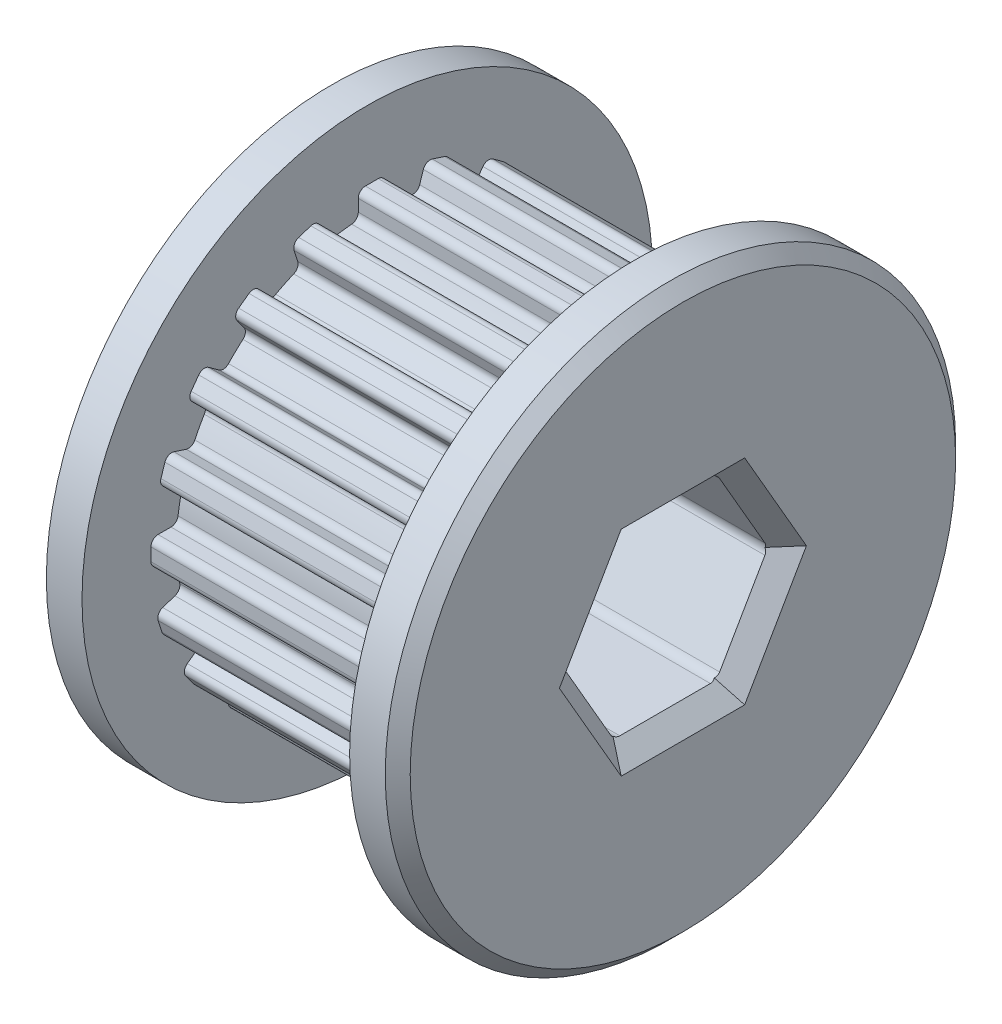
SolidWorks part; units mm, degrees
other "Markup1"
sketch "Sketch5" plane through (2.4288, -10.5, -8) normal (0.9999, -0.0054, -0.0108) x (-0.0109, -0.7875, -0.6163)
material "2024-T4"
ref_plane "Front Plane" through (0, 0, 0) normal (0, 0, 1) x (1, 0, 0)
ref_plane "Top Plane" through (0, 0, 0) normal (0, 1, 0) x (1, 0, 0)
ref_plane "Right Plane" through (0, 0, 0) normal (1, 0, 0) x (0, 0, -1)
sketch "Sketch1" plane through (0, 0, 0) normal (0, 0, 1) x (1, 0, 0)
  line L0 (-7.4276, 0) -> (2.4288, 0)
  line L1 (2.4288, 0) -> (2.4288, 5.15)
  line L2 (2.0788, 5.5) -> (1.0788, 5.5)
  line L3 (0.5724, 3.61) -> (0.5724, 2.85)
  line L4 (0.5724, 2.85) -> (-6.4276, 2.85)
  line L5 (-7.4276, 2.85) -> (-7.4276, 0)
  line L6 (-7.4276, -2.5) -> (8.5724, -2.5) construction
  line L7 (-8.4276, 2.85) -> (-8.4276, -12.6573) construction
  line L8 (-8.4276, 2.85) -> (-8.4276, 0) construction
  line L9 (0.5724, 5.5) -> (-12.4584, 5.5) construction
  line L10 (0.5724, 3.61) -> (-7.4276, 3.61) construction
  line L11 (-6.4276, 2.85) -> (-6.4276, 3.61)
  line L12 (-6.4276, 3.61) -> (-6.4276, 5.5)
  line L13 (-7.4276, 2.85) -> (-7.4276, 3.61)
  line L14 (-7.4276, 3.61) -> (-7.4276, 5.5)
  line L15 (-7.4276, 5.5) -> (-6.4276, 5.5)
  line L16 (-7.4276, 0) -> (8.5724, 0) construction
  line L18 (-7.4276, 2.85) -> (-7.4276, 0) construction
  line L20 (2.4288, 5.15) -> (2.0788, 5.5)
  line L21 (0.5724, 2.85) -> (-7.4276, 2.85) construction
  line L22 (1.0788, 5.5) -> (0.5724, 3.61)
  point P4 (2.4288, 5.5)
  dimension "D2" = 8
  dimension "D3" = 2.5
  dimension "D4" = 8
  dimension "D5" = 5.35
  dimension "D8" = 1
  dimension "D9" = 180
  dimension "D11" = 1.89
  dimension "D12" = 15
  dimension "D13" = 1
  dimension "D6" = 1
  dimension "D7" = 0.76
  dimension "D10" = 1
revolve "Revolve2" add sketch "Sketch1" angle 360 about L6
sketch "Sketch2" plane through (0.5724, 0, 0) normal (-1, 0, 0) x (0, 0, 1)
  line L1 (-0.51, 2.8066) -> (0.25, 2.8066)
  line L2 (-0.51, 2.8066) -> (-0.51, 3.5666)
  line L3 (-0.51, 3.5666) -> (0.25, 3.5666)
  line L4 (0.25, 2.8066) -> (0.25, 3.5666)
  dimension "D1" = 0.76
  dimension "D2" = 0.76
extrude "Boss-Extrude1" add sketch "Sketch2" along normal up to surface (7 mm away) up to face at (-6.4276, -2.5, 8)
fillet "Fillet1" radius 0.2 4 edges at (-2.9276, 2.8256, -0.51) (-2.9276, 2.8442, 0.25) (-2.9276, 3.5666, -0.51) (-2.9276, 3.5666, 0.25)
pattern_circular "CirPattern2" count 20 over 360 about axis through (-7.4276, -2.5, 0) along (-1, 0, 0) of "Boss-Extrude1", "Fillet1"
sketch "Sketch3" plane through (0, 0, 0) normal (0, 1, 0) x (1, 0, 0)
  line L0 (1.0788, -8) -> (2.0788, -8) construction
  line L3 (1.5788, -8) -> (1.5788, 8) construction
  line L4 (2.0788, 8) -> (1.0788, 8) construction
  circle A0 centre (1.5788, 0) radius 1.5
extrude "Cut-Extrude2" [suppressed] cut sketch "Sketch3" against normal blind 3 and the other way blind 9 contours A0
pattern_circular "CirPattern3" [suppressed] count 2 every 90 of bodies 106
sketch "Sketch4" plane through (2.4288, 0, 0) normal (1, 0, 0) x (0, 0, -1)
  line L1 (2.8868, -2.5) -> (1.4434, 0)
  line L2 (1.4434, 0) -> (-1.4434, 0)
  line L3 (-1.4434, 0) -> (-2.8868, -2.5)
  line L4 (-2.8868, -2.5) -> (-1.4434, -5)
  line L5 (-1.4434, -5) -> (1.4434, -5)
  line L6 (1.4434, -5) -> (2.8868, -2.5)
  circle A0 centre (0, -2.5) radius 2.5 construction
  dimension "D1" = 5
extrude "Cut-Extrude3" cut sketch "Sketch4" against normal through all
chamfer "Chamfer1" distance 0.5 angle 45 12 edges at (-7.4276, -1.25, -2.1651) (-7.4276, -3.75, -2.1651) (-7.4276, -5, 0) (-7.4276, -3.75, 2.1651) (-7.4276, -1.25, 2.1651) (-7.4276, 0, 0) (2.4288, -1.25, -2.1651) (2.4288, -3.75, -2.1651) (2.4288, -5, 0) (2.4288, -3.75, 2.1651) (2.4288, -1.25, 2.1651) (2.4288, 0, 0)
fillet "Fillet2" radius 0.3 6 edges at (-2.4994, -2.5, -2.8868) (-2.4994, -5, -1.4434) (-2.4994, -5, 1.4434) (-2.4994, -2.5, 2.8868) (-2.4994, 0, 1.4434) (-2.4994, 0, -1.4434)
